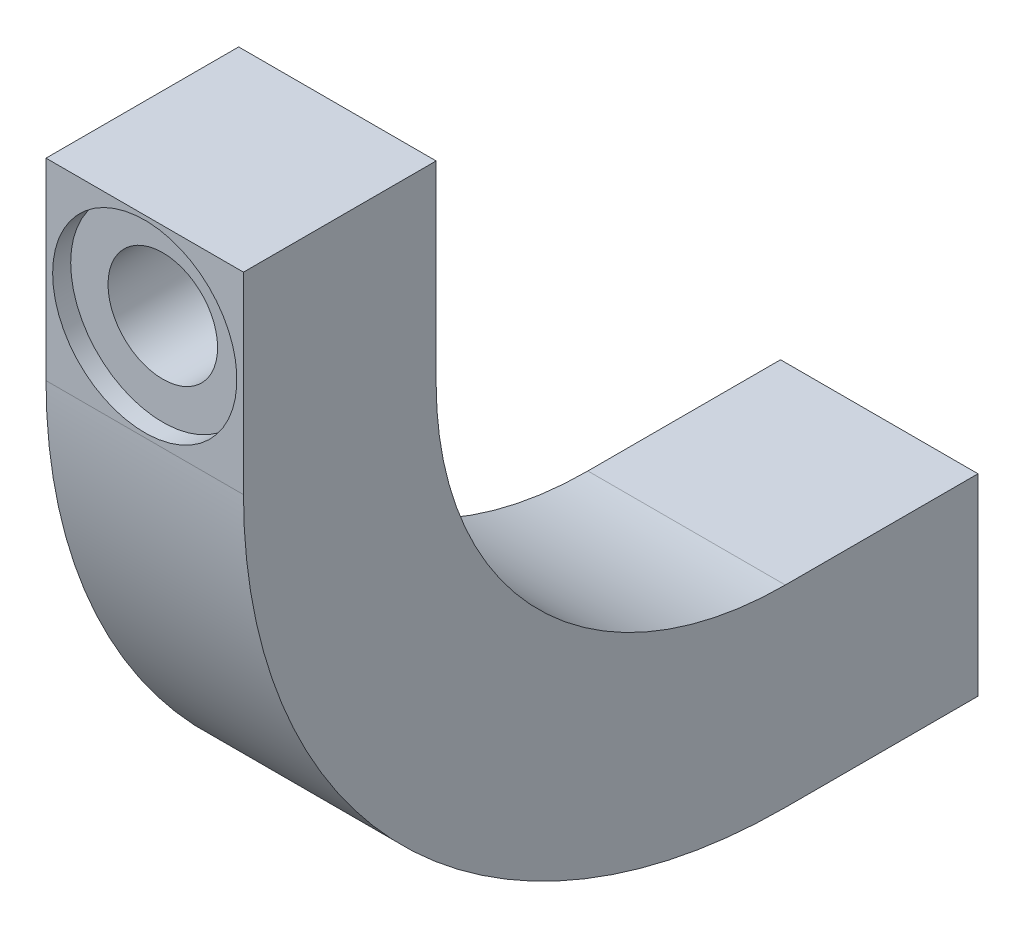
SolidWorks part; units mm, degrees
ref_plane "Front Plane" through (0, 0, 0) normal (0, 0, 1) x (1, 0, 0)
ref_plane "Top Plane" through (0, 0, 0) normal (0, 1, 0) x (1, 0, 0)
ref_plane "Right Plane" through (0, 0, 0) normal (1, 0, 0) x (0, 0, -1)
ref_axis "Z" through (0, 0, 22.75) along (0, 0, -1)
sketch "Sketch4" plane through (0, 0, 0) normal (0, 0, 1) x (1, 0, 0)
  circle A0 centre (0, 0) radius 17.5 construction
  dimension "D1" = 35
sketch "Sketch5" plane through (0, 0, 0) normal (1, 0, 0) x (0, 0, -1)
  line L0 (-18.5, 4) -> (-18.5, 0)
  line L1 (-18.5, 0) -> (-18.5, -4)
  line L2 (-26.5, -4) -> (-26.5, 4)
  line L6 (-26.5, 4) -> (-18.5, 4)
  line L12 (-22.75, 0) -> (-13.0351, 0) construction
  line L13 (0, 0) -> (-14.9091, -14.9091) construction
  line L14 (0, 0) -> (7.0065, 0) construction
  line L15 (0, -18.5) -> (-4, -18.5)
  line L16 (4, -18.5) -> (0, -18.5)
  line L17 (-4, -26.5) -> (4, -26.5)
  line L18 (4, -26.5) -> (4, -18.5)
  circle A0 centre (0, 0) radius 14 construction
  arc A1 (-18.5, -4) -> (-4, -18.5) centre (-4, -4) ccw
  arc A2 (-26.5, -4) -> (-4, -26.5) centre (-4, -4) ccw
  point P2 (9.4307, -21)
  point P4 (0, -2.1363)
  dimension "D1" = 28
  dimension "D4" = 4
  dimension "D2" = 45
  dimension "D3" = 8
  dimension "D5" = 18.5
sketch "Sketch6" plane through (0, 0, 0) normal (0, 1, 0) x (1, 0, 0)
  circle A0 centre (0, 0) radius 17.5 construction
  dimension "D1" = 35
extrude "Boss-Extrude1" add sketch "Sketch5" along normal blind 4.1 and the other way blind 4.1
sketch "Sketch7" plane through (0, 0, 0) normal (0, 0, 1) x (1, 0, 0)
  circle A0 centre (0, 0) radius 1.75
  dimension "D1" = 3.5
extrude "Cut-Extrude1" cut sketch "Sketch7" along normal through all
ref_axis "Y" through (0, -9.3489, 0) along (0, -1, 0)
sketch "Sketch12" plane through (0, 0, 26.5) normal (0, 0, 1) x (1, 0, 0)
  circle A0 centre (0, 0) radius 2.275
  dimension "D1" = 4.55
extrude "Cut-Extrude7" cut sketch "Sketch12" against normal blind 6
sketch "Sketch14" plane through (0, 0, 26.5) normal (0, 0, -1) x (1, 0, 0)
  circle A0 centre (0, 0) radius 3.825
  dimension "D1" = 7.65
extrude "Cut-Extrude10" cut sketch "Sketch14" along normal blind 0.75
ref_plane "Plane1" through (0, -18.5, 0) normal (0, 1, 0) x (1, 0, 0)
ref_axis "CX" through (0, -18.5, 4.4) along (0, 0, -1)
ref_plane "Plane2" through (0, 0, 0) normal (0, 0, -1) x (0, 1, 0)
ref_plane "Plane3" through (0, 0, 0) normal (1, 0, 0) x (0, 0, -1)
ref_axis "CZ" through (0, -8.7018, 0) along (0, -1, 0)
ref_axis "CY" through (-0.6471, -18.5, 0) along (1, 0, 0)
ref_point "CO"
sketch "Sketch15" plane through (0, -26.5, 0) normal (0, -1, 0) x (1, 0, 0)
  circle A0 centre (0, 0) radius 1.5
  dimension "D1" = 3
extrude "Cut-Extrude11" cut sketch "Sketch15" against normal blind 6
equation "\"rbracket-width\"= \"L2Thickness\" + 0.2"
equation "\"EyeCaptureRadius\"= ( \"EyeDiameter\" + \"EyeClearance\" ) / 2"
equation "\"rbracket_planetocenterline_dist\"= \"BasePlaneDistance\""
equation "\"EyeDiameter\" = 35"
equation "\"BasePlaneDistance\" = \"EyeDiameter\"/2+19.84"
equation "\"EyeClearance\" = 2"
equation "\"D1@Sketch4\"=\"EyeDiameter\""
equation "\"D1@Sketch6\"=\"EyeDiameter\""
equation "\"D1@Boss-Extrude1\"=\"rbracket-width\"/2"
equation "\"D2@Boss-Extrude1\"=\"rbracket-width\"/2"
equation "\"L2Thickness\" = 8"
equation "\"D3@Sketch5\"=\"L2Thickness\""
equation "\"D5@Sketch5\"=(\"EyeDiameter\"+\"EyeClearance\")/2"
equation "\"BearingThickness\"= 6"
equation "\"BearingOD\"=4.5"
equation "\"OuterBearingProudDistance\"= 0"
equation "\"D1@Cut-Extrude7\"=\"BearingThickness\"-\"OuterBearingProudDistance\""
equation "\"D1@Sketch12\"= \"BearingOD\" + \"PrinterFilamentThickness\" *\"ApplyPrinterOffset\" / 2"
equation "\"FlangeOD\"=7.5"
equation "\"FlangeThickness\"= 0.75"
equation "\"D1@Sketch14\"=\"FlangeOD\" + \"PrinterFilamentThickness\"*1.5 * \"ApplyPrinterOffset\""
equation "\"D1@Cut-Extrude10\"=\"FlangeThickness\""
equation "\"PrinterFilamentThickness\"= 0.1'For setting distances for things like pressfits"
equation "\"ApplyPrinterOffset\"= 1'Set to 0 for line-to-line. Set to 1 for applying guestimate dimensions to make the printer produce good parts"
equation "\"D1@Cut-Extrude11\"=3*1.5"
